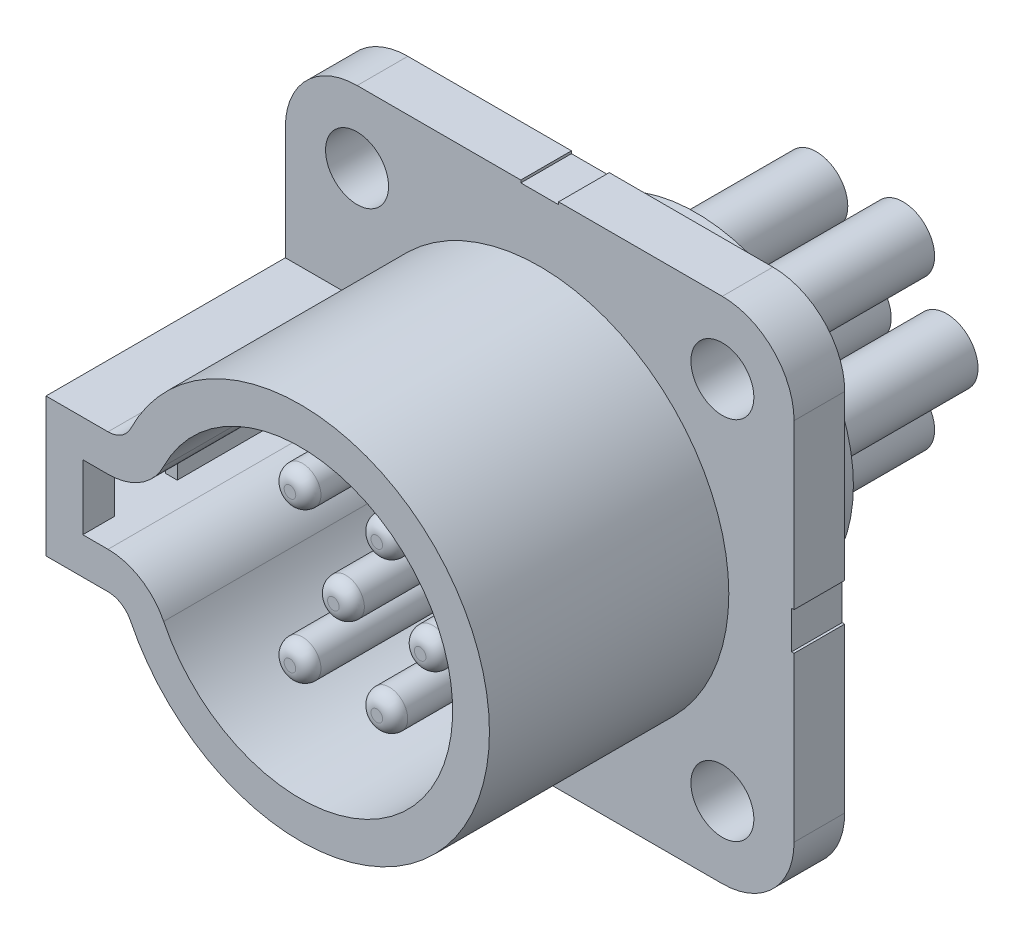
SolidWorks part; units mm, degrees
ref_plane "Front Plane" through (0, 0, 0) normal (0, 0, 1) x (1, 0, 0)
ref_plane "Top Plane" through (0, 0, 0) normal (0, 1, 0) x (1, 0, 0)
ref_plane "Right Plane" through (0, 0, 0) normal (1, 0, 0) x (0, 0, -1)
sketch "Sketch1" plane through (0, 0, 0) normal (0, 0, 1) x (1, 0, 0)
  line L1 (-10.095, 10.095) -> (10.095, 10.095)
  line L2 (-10.095, 10.095) -> (-10.095, -10.095)
  line L3 (-10.095, -10.095) -> (10.095, -10.095)
  line L4 (10.095, 10.095) -> (10.095, -10.095)
  line L5 (-10.095, 10.095) -> (10.095, -10.095) construction
  line L6 (-10.095, -10.095) -> (10.095, 10.095) construction
  point P0 (0, 0)
  dimension "D1" = 20.19
  dimension "D2" = 20.19
extrude "Boss-Extrude1" add sketch "Sketch1" along normal blind 2.01
sketch "Sketch2" plane through (0, 0, 2.01) normal (0, 0, 1) x (1, 0, 0)
  line L0 (0, 0) -> (0, 10.095) construction
  line L1 (10.095, 10.095) -> (-10.095, 10.095) construction
  line L2 (0, 0) -> (-10.095, 0) construction
  line L3 (-10.095, 10.095) -> (-10.095, -10.095) construction
  circle A0 centre (-7.25, 7.25) radius 1.25
  circle A1 centre (7.25, 7.25) radius 1.25
  circle A2 centre (7.25, -7.25) radius 1.25
  circle A3 centre (-7.25, -7.25) radius 1.25
  dimension "D1" = 2.5
  dimension "D2" = 7.25
  dimension "D3" = 7.25
extrude "Cut-Extrude1" cut sketch "Sketch2" against normal up to surface (2.01 mm away) up to face at (0, 0, 0)
fillet "Fillet1" radius 2.85 4 edges at (10.095, -10.095, 1.005) (-10.095, -10.095, 1.005) (10.095, 10.095, 1.005) (-10.095, 10.095, 1.005)
sketch "Sketch4" plane through (0, 0, 2.01) normal (0, 0, 1) x (1, 0, 0)
  line L0 (-10.095, -2.7495) -> (-10.095, 2.7495)
  line L1 (-10.095, 7.245) -> (-10.095, -7.245) construction
  line L2 (-10.095, 2.7495) -> (-7.6339, 2.7495)
  line L3 (-10.095, 0) -> (11.2357, 0) construction
  line L4 (-10.095, -2.7495) -> (-7.6339, -2.7495)
  line L5 (-8.635, -1.2895) -> (-8.635, 1.2895)
  line L6 (-8.635, 1.2895) -> (-7.6339, 1.2895)
  line L7 (-8.635, -1.2895) -> (-7.6339, -1.2895)
  line L8 (0, 10.095) -> (0, -11.6505) construction
  line L9 (7.245, 10.095) -> (-7.245, 10.095) construction
  line L10 (0, 6.045) -> (3.3385, 6.045) construction
  line L11 (0, -6.045) -> (3.3385, -6.045) construction
  line L12 (0, -7.505) -> (3.9298, -7.505) construction
  line L13 (0, 7.505) -> (4.2254, 7.505) construction
  arc A0 (-6.7363, 3.3086) -> (-6.7363, -3.3086) centre (0, 0) cw
  arc A1 (-6.7363, 3.3086) -> (-7.6339, 2.7495) centre (-7.6339, 3.7495) cw
  arc A2 (-6.7363, -3.3086) -> (-7.6339, -2.7495) centre (-7.6339, -3.7495) ccw
  arc A3 (-5.4259, 2.665) -> (-7.6339, 1.2895) centre (-7.6339, 3.7495) cw
  arc A4 (-5.4259, 2.665) -> (-5.4259, -2.665) centre (0, 0) cw
  arc A5 (-5.4259, -2.665) -> (-7.6339, -1.2895) centre (-7.6339, -3.7495) ccw
  dimension "D1" = 1
  dimension "D3" = 15.01
  dimension "D4" = 12.09
extrude "Boss-Extrude2" add sketch "Sketch4" along normal blind 9.5
sketch "Sketch5" plane through (-10.095, 0, 0) normal (-1, 0, 0) x (0, 0, 1)
  line L0 (0, 7.245) -> (0, -7.245) construction
  line L1 (0, 1.2895) -> (10.26, 1.2895)
  line L2 (0, 1.2895) -> (0, -1.2895)
  line L3 (0, -1.2895) -> (10.26, -1.2895)
  line L4 (10.26, 1.2895) -> (10.26, -1.2895)
  line L6 (0, 0) -> (-1.0293, 0) construction
  line L7 (11.51, 2.7495) -> (11.51, -2.7495) construction
  line L8 (11.51, 2.7495) -> (2.01, 2.7495) construction
  line L9 (11.51, -2.7495) -> (2.01, -2.7495) construction
  dimension "D1" = 1.25
  dimension "D2" = 1.46
  dimension "D3" = 1.46
extrude "Cut-Extrude2" cut sketch "Sketch5" against normal blind 1
sketch "Sketch6" plane through (-9.095, 0, 0) normal (-1, 0, 0) x (0, 0, 1)
  line L0 (0, -1.2895) -> (10.26, -1.2895) construction
  line L1 (10.26, 1.2895) -> (7.76, 1.2895)
  line L2 (10.26, 1.2895) -> (10.26, -1.2895)
  line L3 (10.26, -1.2895) -> (7.76, -1.2895)
  line L4 (7.76, 1.2895) -> (7.76, -1.2895)
  dimension "D1" = 2.5
extrude "Cut-Extrude3" cut sketch "Sketch6" against normal up to next
sketch "Sketch7" plane through (0, 0, 0) normal (0, 0, -1) x (-1, 0, 0)
  circle A0 centre (0, 0) radius 6.25
  dimension "D1" = 12.5
extrude "Boss-Extrude3" add sketch "Sketch7" along normal blind 4.19
sketch "Sketch8" plane through (0, 0, 2.01) normal (0, 0, 1) x (1, 0, 0)
  line L0 (-3.445, 0) -> (5.0962, 0) construction
  circle A0 centre (0, 0) radius 0.73
  circle A2 centre (3.445, 0) radius 0.73
  circle A3 centre (1.7225, 2.9835) radius 0.73
  circle A4 centre (-1.7225, 2.9835) radius 0.73
  circle A5 centre (1.7225, -2.9835) radius 0.73
  circle A6 centre (-1.7225, -2.9835) radius 0.73
  dimension "D1" = 1.46
extrude "Boss-Extrude4" add sketch "Sketch8" along normal blind 8.19 and the other way blind 7
fillet "Fillet2" radius 0.5 6 edges at (-2.4525, -2.9835, 10.2) (2.4525, 2.9835, 10.2) (0.9925, -2.9835, 10.2) (4.175, 0, 10.2) (0.73, 0, 10.2) (-0.9925, 2.9835, 10.2)
sketch "Sketch9" plane through (0, 0, -4.19) normal (0, 0, -1) x (-1, 0, 0)
  circle A0 centre (-1.7225, 2.9835) radius 1
  circle A1 centre (1.7225, 2.9835) radius 1
  circle A2 centre (0, 0) radius 1
  circle A3 centre (-3.445, 0) radius 1
  circle A4 centre (-1.7225, -2.9835) radius 1
  circle A5 centre (-1.7225, -2.9835) radius 1
  circle A6 centre (1.7225, -2.9835) radius 1
  point P0 (-1.7225, 2.9835)
  point P1 (1.7225, 2.9835)
  point P3 (-3.445, 0)
  point P5 (0, 0)
  point P7 (-1.7225, -2.9835)
  point P9 (1.7225, -2.9835)
  dimension "D1" = 2
  dimension "D2" = 2
  dimension "D3" = 2
  dimension "D4" = 2
  dimension "D5" = 2
  dimension "D6" = 2
extrude "Extrude-Thin1" add sketch "Sketch9" along normal blind 6.5 thin contours A0 | A1 | A2 | A3 | A4 | A6 thin type one direction wall 0.25
sketch "Sketch10" plane through (0, 10.095, 0) normal (0, 1, 0) x (1, 0, 0)
  line L0 (7.245, 0) -> (-7.245, 0) construction
  line L1 (-0.75, 0) -> (0.75, 0)
  line L2 (-0.75, 0) -> (-0.75, -2.01)
  line L3 (-0.75, -2.01) -> (0.75, -2.01)
  line L4 (0.75, 0) -> (0.75, -2.01)
  line L5 (7.245, -2.01) -> (-7.245, -2.01) construction
  line L6 (0, 4.99) -> (0, -4.274) construction
  line L7 (0.73, 4.99) -> (-0.73, 4.99) construction
  point P10 (0, -2.01)
  dimension "D1" = 1.5
  dimension "D2" = 0
extrude "Cut-Extrude4" cut sketch "Sketch10" against normal blind 0.1
sketch "Sketch12" plane through (10.095, 0, 0) normal (1, 0, 0) x (0, 0, -1)
  line L0 (-11.51, 0) -> (5.9037, 0)
  line L1 (-11.51, 7.505) -> (-11.51, -7.505) construction
  line L2 (0, -7.245) -> (0, 7.245) construction
  line L3 (-2.01, 0.75) -> (0, 0.75)
  line L4 (-2.01, 0.75) -> (-2.01, -0.75)
  line L5 (-2.01, -0.75) -> (0, -0.75)
  line L6 (0, 0.75) -> (0, -0.75)
  line L7 (-2.01, 0.75) -> (0, -0.75) construction
  line L8 (-2.01, -0.75) -> (0, 0.75) construction
  line L9 (-2.01, -7.245) -> (-2.01, 7.245) construction
  point P5 (-1.005, 0)
  dimension "D1" = 1.5
extrude "Cut-Extrude5" cut sketch "Sketch12" against normal blind 0.1 contours L3 L6 L5 L4
equation "\"D2@Sketch1\"=\"D1@Sketch1\""
equation "\"D3@Sketch5\"=\"D2@Sketch5\""
equation "\"D2@Sketch9\"=\"D1@Sketch9\""
equation "\"D3@Sketch9\"=\"D1@Sketch9\""
equation "\"D4@Sketch9\"=\"D1@Sketch9\""
equation "\"D5@Sketch9\"=\"D1@Sketch9\""
equation "\"D6@Sketch9\"=\"D1@Sketch9\""
